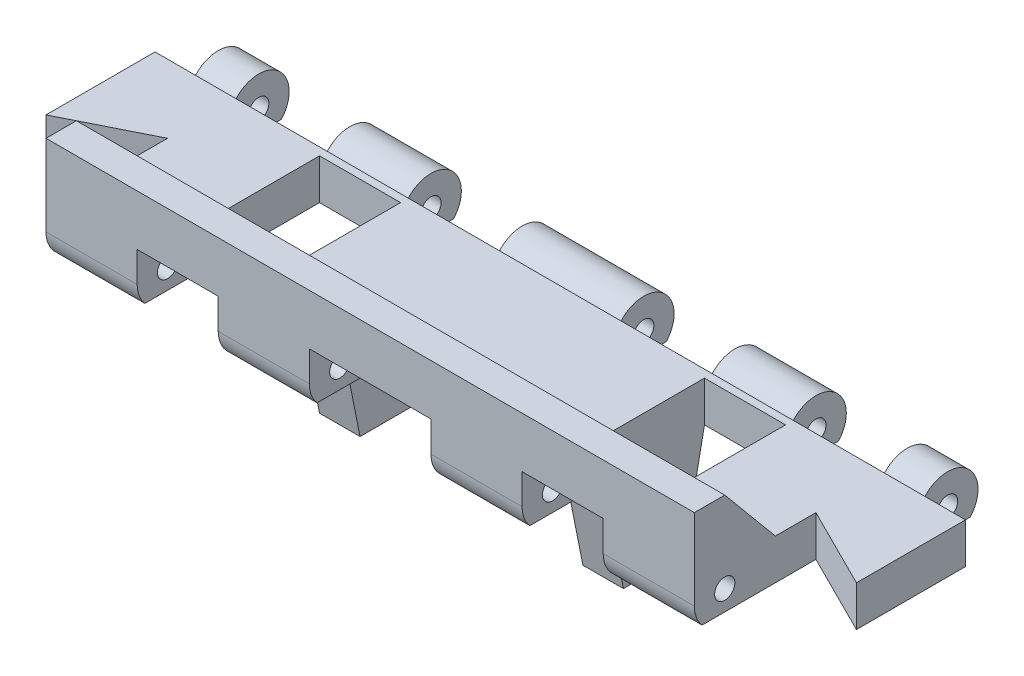
SolidWorks part; units mm, degrees
ref_plane "Alzado" through (0, 0, 0) normal (0, 0, 1) x (1, 0, 0)
ref_plane "Planta" through (0, 0, 0) normal (0, 1, 0) x (1, 0, 0)
ref_plane "Vista lateral" through (0, 0, 0) normal (1, 0, 0) x (0, 0, -1)
sketch "Croquis1" plane through (0, 0, 0) normal (0, 1, 0) x (1, 0, 0)
  line L0 (-20, 0) -> (20, 0)
  line L1 (-11.5, 0) -> (11.5, 0)
  line L2 (-7.5, 0) -> (7.5, 0)
  line L3 (-11.5, 0) -> (-11.5, -5)
  line L4 (-7.5, 0) -> (-7.5, -5)
  line L5 (7.5, 0) -> (7.5, -5)
  line L6 (11.5, 0) -> (11.5, -5)
  line L7 (-20, 0) -> (-20, -5)
  line L8 (20, 0) -> (20, -5)
  line L9 (-20, 0) -> (-16, 0)
  line L10 (20, 0) -> (16, 0)
  line L11 (-16, 0) -> (-16, -3)
  line L12 (16, 0) -> (16, -3)
  line L13 (-20, -5) -> (-16, -3)
  line L14 (20, -5) -> (16, -3)
  line L15 (-16, 0) -> (-16, -6)
  line L16 (16, 0) -> (16, -6)
  line L17 (-16, -6) -> (16, -6)
  line L18 (-11.5, -5) -> (-7.5, -5)
  line L19 (7.5, -5) -> (11.5, -5)
  point P4 (0, 0)
  point P8 (0, 0)
  point P11 (0, 0)
extrude "Saliente-Extruir1" add sketch "Croquis1" along normal blind 1 and the other way blind 1 contours L7 L13 L11 L0 | L19 L5 L1 L4 L18 L3 L0 L11 L15 L17 L16 L12 L6 | L14 L8 L0 L12 region at (-18.1667, 0, 2.0417) region at (0, 0, 3.1316) region at (18.1667, 0, 2.0417)
sketch "Croquis2" plane through (20, 0, 0) normal (1, 0, 0) x (0, 0, -1)
  line L0 (0, 0) -> (1.5, 0)
  line L2 (1.5, 0) -> (1, 0)
  line L3 (0, 1) -> (0.382, 1)
  line L4 (0, -1) -> (0.382, -1)
  line L5 (0, -1) -> (0, 1)
  line L6 (0.382, -1) -> (0, -1)
  line L7 (0, -1) -> (0, 0)
  line L8 (0, 0) -> (0, 1)
  circle A1 centre (1.5, 0) radius 0.5
  circle A2 centre (1.5, 0) radius 1.5
  arc A3 (0.382, 1) -> (0, 0) centre (1.5, 0) ccw
  arc A4 (0, 0) -> (0.382, -1) centre (1.5, 0) ccw
  line M2 (0, -1) -> (0, 1)
extrude "Saliente-Extruir2" add sketch "Croquis2" against normal blind 40 contours A2 L4 M2 | A2 L3 M2 | A2 A1 region at (20, -0.7568, -0.1116) region at (20, 0.7568, -0.1116) region at (20, 0.5201, -0.1384)
sketch "Croquis5" plane through (20, 0, 0) normal (1, 0, 0) x (0, 0, -1)
  line L0 (0.382, -1) -> (2.618, -1)
  line L1 (0.382, -1) -> (2.618, -1)
  arc A0 (0.382, -1) -> (0.382, 1) centre (1.5, 0) ccw construction
  arc A1 (2.618, -1) -> (0.382, -1) centre (1.5, 0) cw
  arc M2 (0.382, -1) -> (0.382, 1) centre (1.5, 0) ccw
extrude "Cortar-Extruir1" cut sketch "Croquis5" against normal blind 40 contours L0 M2 region at (20, -1.2032, -1.5)
sketch "Croquis6" plane through (20, 0, 0) normal (1, 0, 0) x (0, 0, -1)
  line L0 (0.382, 1) -> (0.382, -1)
  line L1 (2.618, -1) -> (-5, -1) construction
  line L2 (0.382, -1) -> (2.618, -1)
  arc A0 (0.382, 1) -> (2.618, -1) centre (1.5, 0) cw
  arc A1 (2.618, -1) -> (0.382, 1) centre (1.5, 0) ccw construction
  circle M1 centre (1.5, 0) radius 0.5
  line M2 (-5, -1) -> (2.618, -1)
  arc M3 (2.618, -1) -> (0.382, 1) centre (1.5, 0) ccw
extrude "Cortar-Extruir2" cut sketch "Croquis6" against normal blind 2 contours L0 M3 M2 M1 region at (20, 1.0911, -2.4759)
sketch "Croquis7" plane through (-20, 0, 0) normal (-1, 0, 0) x (0, 0, 1)
  line L0 (-0.382, 1) -> (-0.382, -1)
  line L1 (-0.382, -1) -> (-2.618, -1)
  arc A0 (-0.382, 1) -> (-0.382, -1) centre (-1.5, 0) cw
  circle M1 centre (-1.5, 0) radius 0.5
  arc M2 (-0.382, 1) -> (-2.618, -1) centre (-1.5, 0) ccw
  line M3 (-2.618, -1) -> (5, -1)
extrude "Cortar-Extruir3" cut sketch "Croquis7" against normal blind 2 contours L0 M2 M3 M1 region at (-20, 0, -0.4182)
sketch "Croquis9" plane through (-16, 0, 0) normal (-1, 0, 0) x (0, 0, 1)
  line L0 (6, 0) -> (7.5, 0)
  line L1 (7.5, 0) -> (7, 0)
  line L2 (6, -1) -> (6, 1) construction
  line L3 (6, 1) -> (6, -1)
  line L4 (6, -1) -> (6.382, -1)
  line L5 (6, 1) -> (6.382, 1)
  line L6 (9, 0) -> (9, 4)
  line L7 (9, 4) -> (7.5, 4)
  line L8 (7.5, 4) -> (5, 1)
  line L9 (5, 1) -> (6, 1)
  circle A0 centre (7.5, 0) radius 0.5
  circle A1 centre (7.5, 0) radius 1.5
  line M3 (6, -1) -> (6, 1)
  line M4 (6, 1) -> (3, 1)
extrude "Saliente-Extruir3" add sketch "Croquis9" against normal blind 32 contours A1 L6 L7 L8 L5 M4 | A1 A0 | A1 L5 M3 | A1 L4 M3 region at (-16, -0.7568, 6.1116) region at (-16, 0.7568, 6.1116) region at (-16, 0.5201, 6.1384) region at (-16, 2.3578, 7.5549)
sketch "Croquis10" plane through (-16, 0, 0) normal (-1, 0, 0) x (0, 0, 1)
  line L0 (6.382, -1) -> (8.618, -1)
  line L1 (3, -1) -> (6.382, -1) construction
  arc A0 (6.382, -1) -> (9, 0) centre (7.5, 0) ccw construction
  arc A1 (8.618, -1) -> (6.382, -1) centre (7.5, 0) cw
  arc M3 (6.382, -1) -> (9, 0) centre (7.5, 0) ccw
extrude "Cortar-Extruir4" cut sketch "Croquis10" against normal blind 36 contours L0 M3 region at (-16, -1.2032, 7.5)
sketch "Croquis11" plane through (0, -1, 0) normal (0, -1, 0) x (1, 0, 0)
  line L0 (-18, -0.382) -> (-16, -0.382)
  line L1 (-18, -0.382) -> (18, -0.382) construction
  line L2 (-16, -0.382) -> (-16, -3)
  line L3 (-18, -3) -> (18, -3) construction
  line L4 (-16, -0.382) -> (-11.5, -0.382)
  line L5 (-11.5, -0.382) -> (-11.5, -3)
  line L6 (-18, -3) -> (18, -3) construction
  line L7 (-11.5, -3) -> (-16, -3)
  line L8 (18, -0.382) -> (16, -0.382)
  line L9 (16, -0.382) -> (11.5, -0.382)
  line L10 (11.5, -0.382) -> (11.5, -3)
  line L11 (-18, -3) -> (18, -3) construction
  line L12 (11.5, -3) -> (16, -3)
  line L13 (-18, -3) -> (18, -3) construction
  line L14 (16, -3) -> (16, -0.382)
  line L15 (11.5, -0.382) -> (7.5, -0.382)
  line L16 (7.5, -0.382) -> (3, -0.382)
  line L17 (-11.5, -0.382) -> (-7.5, -0.382)
  line L18 (-7.5, -0.382) -> (-3, -0.382)
  line L19 (7.5, -0.382) -> (7.5, -3)
  line L20 (7.5, -3) -> (3, -3)
  line L21 (-18, -3) -> (18, -3) construction
  line L22 (3, -3) -> (3, -0.382)
  line L23 (-3, -0.382) -> (-3, -3)
  line L24 (-18, -3) -> (18, -3) construction
  line L25 (-3, -3) -> (-7.5, -3)
  line L26 (-18, -3) -> (18, -3) construction
  line L27 (-7.5, -3) -> (-7.5, -0.382)
  line M11 (-18, -2.618) -> (18, -2.618)
extrude "Cortar-Extruir5" cut sketch "Croquis11" against normal blind 36 contours L14 L9 L10 M11 | L22 L19 L16 M11 | L27 L23 L18 M11 | L5 L4 L2 M11 | L7 L5 L2 M11 | L27 L25 L23 M11 | L22 L20 L19 M11 | L12 L14 L10 M11 region at (-13.75, -1, -1.5) region at (5.25, -1, -1.5) region at (5.25, -1, -2.809) region at (-13.75, -1, -2.809) region at (-5.25, -1, -1.5) region at (-5.25, -1, -2.809) region at (13.75, -1, -2.809) region at (13.75, -1, -1.5)
sketch "Croquis14" plane through (0, 0, 9) normal (0, 0, 1) x (1, 0, 0)
  line L0 (16, -1) -> (16, 1.5)
  line L1 (16, 1.5) -> (11.5, 1.5)
  line L2 (11.5, 1.5) -> (7.5, 1.5)
  line L3 (11.5, 1.5) -> (11.5, -1)
  line L4 (11.5, -1) -> (7.5, -1)
  line L5 (7.5, -1) -> (7.5, 1.5)
  line L6 (7.5, 1.5) -> (3, 1.5)
  line L7 (3, 1.5) -> (-3, 1.5)
  line L8 (3, 1.5) -> (3, -1)
  line L9 (3, -1) -> (-3, -1)
  line L10 (-3, -1) -> (-3, 1.5)
  line L11 (-3, 1.5) -> (-7.5, 1.5)
  line L12 (-7.5, 1.5) -> (-11.5, 1.5)
  line L13 (-7.5, 1.5) -> (-7.5, -1)
  line L14 (-16, -1) -> (16, -1) construction
  line L15 (-7.5, -1) -> (-11.5, -1)
  line L16 (-11.5, -1) -> (-11.5, 1.5)
  line M2 (-16, 0) -> (16, 0)
extrude "Cortar-Extruir6" cut sketch "Croquis14" against normal blind 3 contours L16 L13 L12 M2 | L16 L15 L13 M2 | L10 L8 L7 M2 | L10 L9 L8 M2 | L5 L3 L2 M2 | L5 L4 L3 M2 region at (9.5, 0.75, 9) region at (9.5, -0.5, 9) region at (0, 0.75, 9) region at (0, -0.5, 9) region at (-9.5, 0.75, 9) region at (-9.5, -0.5, 9)
sketch "Croquis15" plane through (-7.5, 0, 0) normal (-1, 0, 0) x (0, 0, 1)
  line L0 (0, -1) -> (0, -6)
  line L1 (5, -1) -> (5, -6)
  line L2 (0, -6) -> (5, -6)
  line L3 (1, -6) -> (4, -6)
  line L4 (1, -6) -> (0, -1)
  line L5 (4, -6) -> (5, -1)
  line L6 (0, -1) -> (5, -1)
  point P10 (2.5, -6)
  line M4 (0, -1) -> (5, -1)
extrude "Saliente-Extruir4" add sketch "Croquis15" against normal blind 2 contours L2 L5 L4 M4 region at (-7.5, -3.2917, 2.5)
sketch "Croquis16" plane through (7.5, 0, 0) normal (1, 0, 0) x (0, 0, -1)
  line L0 (-5, -1) -> (-5, -6)
  line L1 (0, -1) -> (0, -6)
  line L2 (-5, -6) -> (0, -6)
  line L3 (-4, -6) -> (-1, -6)
  line L4 (-1, -6) -> (0, -1)
  line L6 (-4, -6) -> (-5, -1)
  line L7 (-5, -1) -> (0, -1)
  point P10 (-2.5, -6)
  point P63 (0, -1)
  line M4 (-5, -1) -> (0, -1)
extrude "Saliente-Extruir5" add sketch "Croquis16" against normal blind 2 contours L6 L2 L4 M4 region at (7.5, -3.2917, 2.5)
